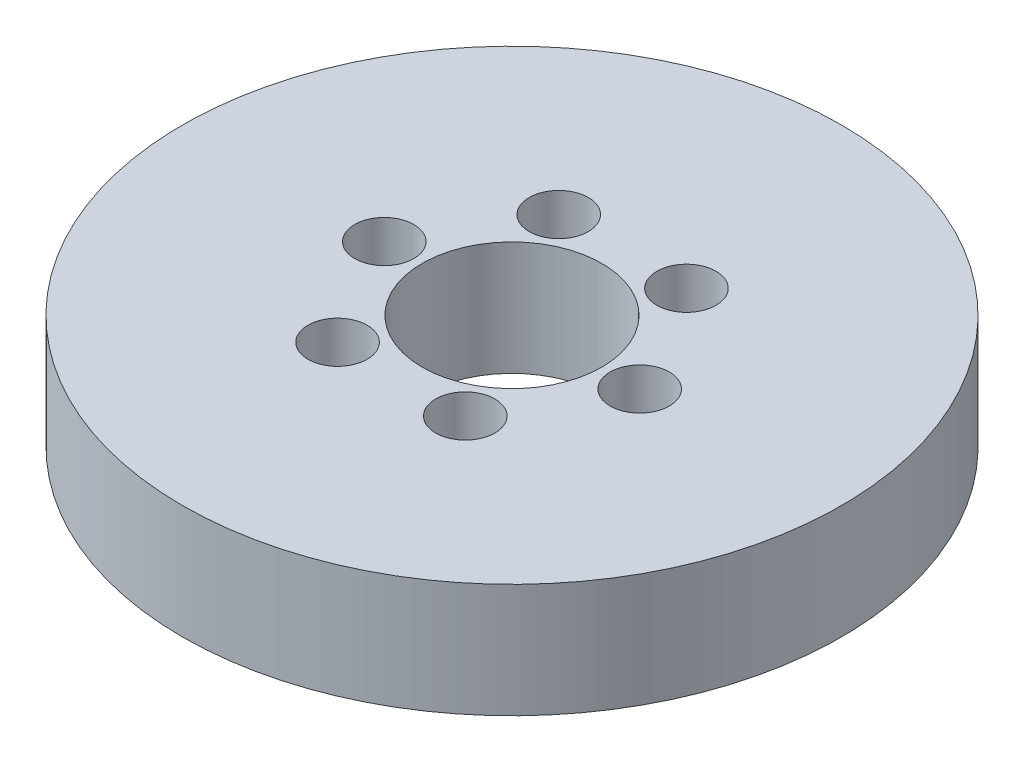
SolidWorks part; units mm, degrees
ref_plane "Front Plane" through (0, 0, 0) normal (0, 0, 1) x (1, 0, 0)
ref_plane "Top Plane" through (0, 0, 0) normal (0, 1, 0) x (1, 0, 0)
ref_plane "Right Plane" through (0, 0, 0) normal (1, 0, 0) x (0, 0, -1)
sketch "Sketch1" plane through (0, 0, 0) normal (0, 1, 0) x (1, 0, 0)
  circle A0 centre (0, 0) radius 55
  dimension "FLANGE_OD" = 110
extrude "Boss-Extrude1" add sketch "Sketch1" along normal blind 19
sketch "Sketch2" plane through (0, 0, 0) normal (0, 1, 0) x (1, 0, 0)
  circle A0 centre (0, 0) radius 15
  dimension "BORE_D" = 30
extrude "Cut-Extrude1" cut sketch "Sketch2" along normal through all
sketch "Sketch3" plane through (0, 19, 0) normal (0, 1, 0) x (1, 0, 0)
  circle A0 centre (0, 0) radius 21.3132 construction
  circle A1 centre (-21.3132, 0) radius 4.9341
  dimension "BOLT_D" = 9.8681
  dimension "BOLT_PCD" = 42.6264
extrude "Cut-Extrude2" cut sketch "Sketch3" against normal blind 16.2004
pattern_circular "CirPattern1" count 6 over 360 about axis through (0, 0, 0) along (0, 1, 0) of "Cut-Extrude2"
